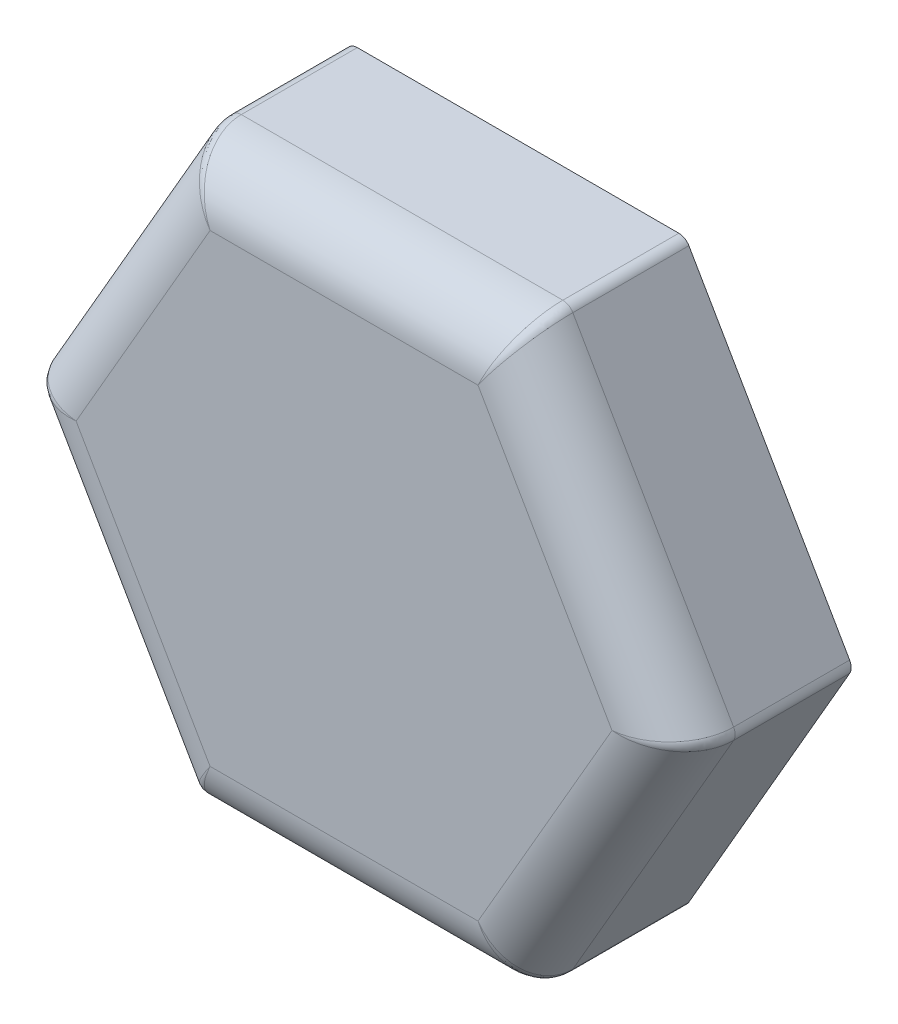
SolidWorks part; units mm, degrees
material "Dostosowane tworzywo sztuczne"
ref_plane "Płaszczyzna przednia" through (0, 0, 0) normal (0, 0, 1) x (1, 0, 0)
ref_plane "Płaszczyzna górna" through (0, 0, 0) normal (0, 1, 0) x (1, 0, 0)
ref_plane "Płaszczyzna prawa" through (0, 0, 0) normal (1, 0, 0) x (0, 0, -1)
sketch "Szkic1" plane through (0, 0, 0) normal (0, 0, 1) x (1, 0, 0)
  line L1 (14.4338, -25) -> (28.8675, 0)
  line L2 (28.8675, 0) -> (14.4338, 25)
  line L3 (14.4338, 25) -> (-14.4338, 25)
  line L4 (-14.4338, 25) -> (-28.8675, 0)
  line L5 (-28.8675, 0) -> (-14.4338, -25)
  line L6 (-14.4338, -25) -> (14.4338, -25)
  circle A0 centre (0, 0) radius 25 construction
  point P10 (0, 0)
  dimension "D1" = 50
extrude "Dodanie-wyciągnięcie1" add sketch "Szkic1" along normal blind 15
fillet "Zaokrąglenie1" radius 5 6 edges at (0, 25, 15) (-21.6506, 12.5, 15) (-21.6506, -12.5, 15) (0, -25, 15) (21.6506, -12.5, 15) (21.6506, 12.5, 15)
fillet "Zaokrąglenie2" radius 1 12 edges at (-13.5882, 23.5355, 13.5355) (-27.1765, 0, 13.5355) (-13.5882, -23.5355, 13.5355) (13.5882, -23.5355, 13.5355) (27.1765, 0, 13.5355) (13.5882, 23.5355, 13.5355) (-14.4338, 25, 5) (-28.8675, 0, 5) (-14.4338, -25, 5) (14.4338, -25, 5) (28.8675, 0, 5) (14.4338, 25, 5)
sketch "Szkic3" plane through (0, 0, 0) normal (0, 0, -1) x (-1, 0, 0)
  line L0 (13.8564, -25) -> (-13.8564, -25) construction
  line L1 (4.6188, -8) -> (9.2376, 0)
  line L2 (9.2376, 0) -> (4.6188, 8)
  line L3 (4.6188, 8) -> (-4.6188, 8)
  line L4 (-4.6188, 8) -> (-9.2376, 0)
  line L5 (-9.2376, 0) -> (-4.6188, -8)
  line L6 (-4.6188, -8) -> (4.6188, -8)
  circle A0 centre (0, 0) radius 11
  circle A1 centre (0, 0) radius 8 construction
  dimension "D2" = 3
  dimension "D1" = 16
extrude "Dodanie-wyciągnięcie2" add sketch "Szkic3" along normal blind 6
